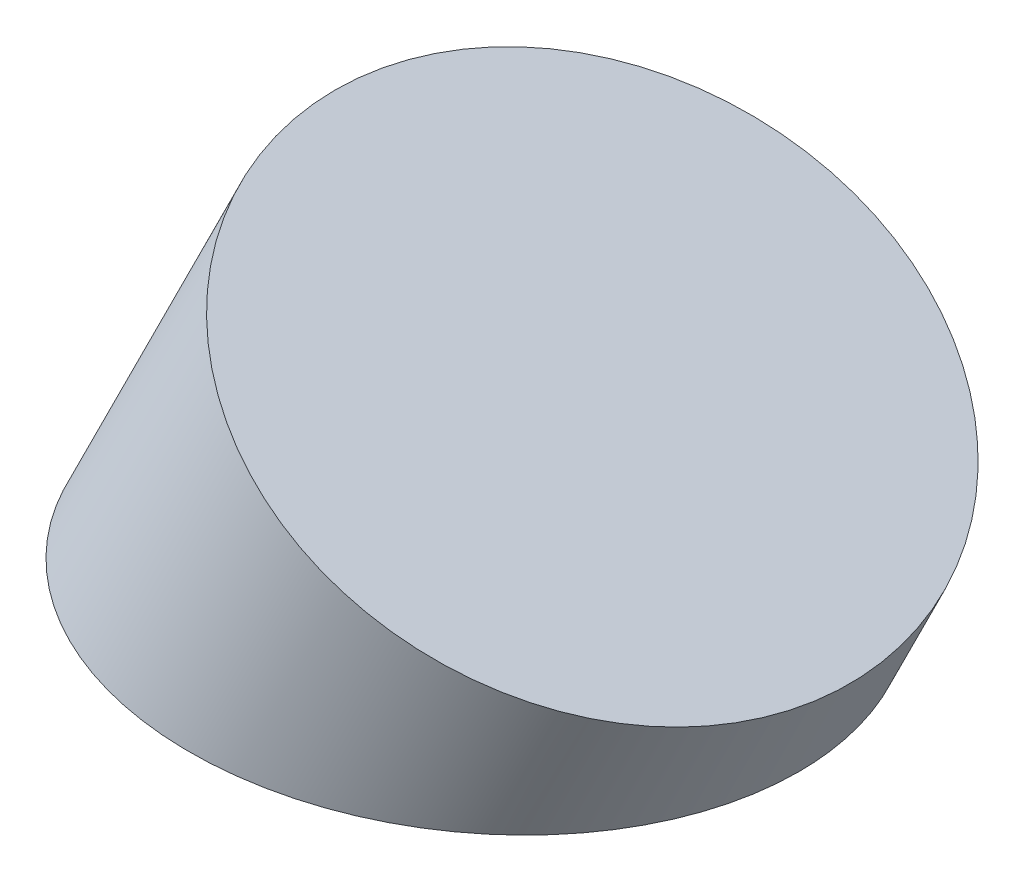
SolidWorks part; units mm, degrees
ref_plane "Front Plane" through (0, 0, 0) normal (0, 0, 1) x (1, 0, 0)
ref_plane "Top Plane" through (0, 0, 0) normal (0, 1, 0) x (1, 0, 0)
ref_plane "Right Plane" through (0, 0, 0) normal (1, 0, 0) x (0, 0, -1)
sketch "Sketch1" plane through (0, 0, 0) normal (0, 0, 1) x (1, 0, 0)
  line L0 (0, 0) -> (50.8, 0)
  line L1 (50.8, 0) -> (0, 25.4)
  line L2 (0, 25.4) -> (0, 0)
  dimension "D1" = 26.565
  dimension "D2" = 50.8
extrude "Boss-Extrude1" add sketch "Sketch1" along normal blind 33.02 and the other way blind 33.02
sketch "Sketch2" plane through (10.16, 20.32, 0) normal (0.4472, 0.8944, 0) x (0.8944, -0.4472, 0)
  line L0 (-11.3592, 0) -> (45.4369, 0)
  line L1 (-11.3592, 33.02) -> (-11.3592, -33.02) construction
  line L2 (45.4369, 33.02) -> (45.4369, -33.02) construction
  line L3 (17.0388, -33.02) -> (17.0388, 33.02)
  line L4 (45.4369, -33.02) -> (-11.3592, -33.02) construction
  line L5 (45.4369, 33.02) -> (-11.3592, 33.02) construction
  circle A1 centre (17.0388, 0) radius 15.875
  line M3 (-11.3592, 33.02) -> (-11.3592, -33.02)
  line M4 (-11.3592, -33.02) -> (45.4369, -33.02)
  line M5 (45.4369, -33.02) -> (45.4369, 33.02)
  line M6 (45.4369, 33.02) -> (-11.3592, 33.02)
  dimension "D1" = 31.75
extrude "Cut-Extrude1" cut sketch "Sketch2" against normal blind 32.004 contours A1 L3 L0 M6 M3 | A1 L0 L3 M5 M6 | A1 L3 L0 M4 M5 | A1 L0 L3 M3 M4 region at (39.8856, 5.4572, -19.1247) region at (39.8856, 5.4572, 19.1247) region at (10.9144, 19.9428, -19.1247) region at (10.9144, 19.9428, 19.1247)
sketch "Sketch5" plane through (10.16, 20.32, 0) normal (0.4472, 0.8944, 0) x (0.8944, -0.4472, 0)
  line L0 (1.1638, 0) -> (32.6337, 0)
  circle A0 centre (17.0388, 0) radius 15.875 construction
